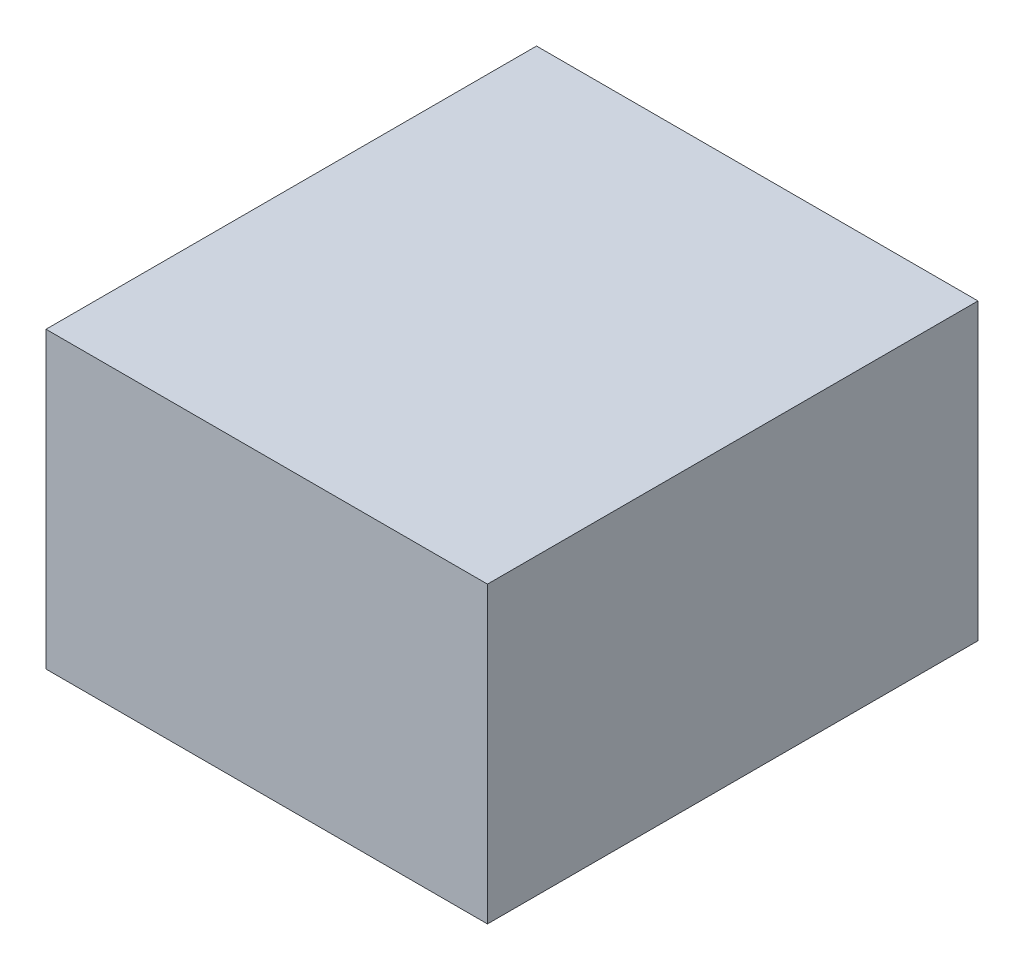
SolidWorks part; units mm, degrees
ref_plane "Front Plane" through (0, 0, 0) normal (0, 0, 1) x (1, 0, 0)
ref_plane "Top Plane" through (0, 0, 0) normal (0, 1, 0) x (1, 0, 0)
ref_plane "Right Plane" through (0, 0, 0) normal (1, 0, 0) x (0, 0, -1)
sketch "Sketch1" plane through (0, 0, 0) normal (0, 1, 0) x (1, 0, 0)
  line L0 (-457.2, 508) -> (457.2, -508) construction
  line L1 (-457.2, 508) -> (457.2, 508)
  line L2 (-457.2, 508) -> (-457.2, -508)
  line L3 (-457.2, -508) -> (457.2, -508)
  line L4 (457.2, 508) -> (457.2, -508)
  dimension "D1" = 914.4
  dimension "D2" = 1016
extrude "Boss-Extrude1" add sketch "Sketch1" along normal mid plane 609.6
